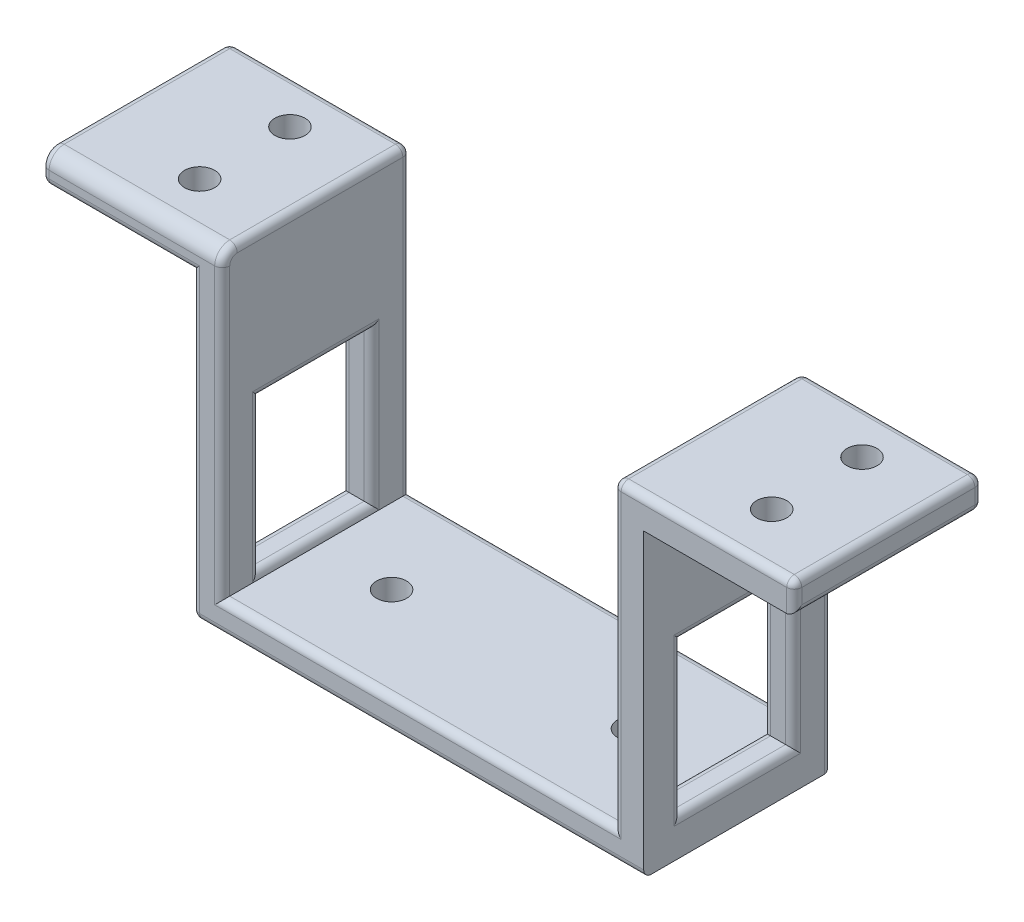
SolidWorks part; units mm, degrees
ref_plane "Front Plane" through (0, 0, 0) normal (0, 0, 1) x (1, 0, 0)
ref_plane "Top Plane" through (0, 0, 0) normal (0, 1, 0) x (1, 0, 0)
ref_plane "Right Plane" through (0, 0, 0) normal (1, 0, 0) x (0, 0, -1)
sketch "Sketch1" plane through (0, 0, 0) normal (0, 1, 0) x (1, 0, 0)
  line L1 (0, 0) -> (60, 0)
  line L2 (0, 0) -> (0, -25)
  line L3 (0, -25) -> (60, -25)
  line L4 (60, 0) -> (60, -25)
  dimension "D1" = 60
  dimension "D2" = 25
extrude "Boss-Extrude1" add sketch "Sketch1" along normal blind 4
sketch "Sketch2" plane through (0, 4, 0) normal (0, 1, 0) x (1, 0, 0)
  line L0 (0, -25) -> (60, -25) construction
  line L1 (0, 0) -> (4, 0)
  line L2 (0, 0) -> (0, -25)
  line L3 (0, -25) -> (4, -25)
  line L4 (4, 0) -> (4, -25)
  line L6 (60, 0) -> (56, 0)
  line L7 (60, 0) -> (60, -25)
  line L8 (60, -25) -> (56, -25)
  line L9 (56, 0) -> (56, -25)
  dimension "D1" = 4
  dimension "D2" = 4
extrude "Boss-Extrude2" add sketch "Sketch2" along normal blind 40
sketch "Sketch3" plane through (60, 0, 0) normal (1, 0, 0) x (0, 0, -1)
  line L0 (0, 44) -> (0, 0) construction
  line L1 (-25, 44) -> (0, 44)
  line L2 (-25, 44) -> (-25, 40)
  line L3 (-25, 40) -> (0, 40)
  line L4 (0, 44) -> (0, 40)
  dimension "D1" = 4
extrude "Boss-Extrude3" add sketch "Sketch3" along normal blind 20
sketch "Sketch4" plane through (0, 0, 0) normal (-1, 0, 0) x (0, 0, 1)
  line L0 (25, 44) -> (25, 0) construction
  line L1 (0, 44) -> (25, 44)
  line L2 (0, 44) -> (0, 40)
  line L3 (0, 40) -> (25, 40)
  line L4 (25, 44) -> (25, 40)
  dimension "D1" = 4
extrude "Boss-Extrude4" add sketch "Sketch4" along normal blind 20
sketch "Sketch5" plane through (0, 44, 0) normal (0, 1, 0) x (1, 0, 0)
  line L0 (56, -25) -> (80, -25) construction
  line L1 (-20, -25) -> (4, -25) construction
  line L2 (4, -25) -> (4, 0) construction
  line L3 (80, 0) -> (80, -25) construction
  circle A0 centre (-6, -6) radius 2
  circle A1 centre (-6, -18) radius 2
  circle A2 centre (70, -6) radius 2
  circle A3 centre (70, -18) radius 2
  dimension "D1" = 4
  dimension "D2" = 4
  dimension "D3" = 4
  dimension "D4" = 4
  dimension "D7" = 7
  dimension "D8" = 7
  dimension "D5" = 12
  dimension "D6" = 12
  dimension "D9" = 10
  dimension "D10" = 10
  dimension "D11" = 10
extrude "Cut-Extrude1" cut sketch "Sketch5" against normal blind 20
sketch "Sketch10" plane through (0, 0, 0) normal (-1, 0, 0) x (0, 0, 1)
  line L0 (0, 0) -> (25, 0) construction
  line L1 (5.1489, 25) -> (20, 25)
  line L2 (5.1489, 25) -> (5.1489, 5)
  line L3 (5.1489, 5) -> (20, 5)
  line L4 (20, 25) -> (20, 5)
  line L5 (25, 40) -> (25, 0) construction
  point P6 (12.5744, 5)
  dimension "D1" = 5
  dimension "D2" = 5
  dimension "D3" = 20
extrude "Cut-Extrude3" cut sketch "Sketch10" against normal blind 75
sketch "Sketch11" plane through (0, 4, 0) normal (0, 1, 0) x (1, 0, 0)
  line L0 (56, 0) -> (56, -25) construction
  line L1 (4, -25) -> (4, 0) construction
  line L2 (56, 0) -> (4, 0) construction
  circle A0 centre (14, -12.5) radius 2
  circle A1 centre (46, -12.5) radius 2
  dimension "D1" = 4
  dimension "D2" = 4
  dimension "D3" = 10
  dimension "D4" = 10
  dimension "D5" = 12.5
  dimension "D6" = 12.5
extrude "Cut-Extrude4" cut sketch "Sketch11" against normal blind 75
fillet "Fillet1" radius 2 1 edges at (-8, 44, 25)
fillet "Fillet2" radius 1 6 edges at (4, 44, 11.5) (4, 23, 25) (-20, 41, 25) (-20, 44, 11.5) (4, 43.4142, 24.4142) (-20, 43.4142, 24.4142)
fillet "Fillet3" radius 1 1 edges at (68, 44, 25)
fillet "Fillet4" radius 1 3 edges at (56, 23.5, 25) (56, 43.7071, 24.7071) (56, 44, 12)
fillet "Fillet5" radius 1 1 edges at (30, 4, 25)
fillet "Fillet6" radius 1 1 edges at (0, 5, 12.5744)
fillet "Fillet7" radius 1 1 edges at (0, 14.5, 5.1489)
fillet "Fillet8" radius 1 1 edges at (0, 25, 12.0744)
fillet "Fillet9" radius 1 1 edges at (0, 20, 25)
fillet "Fillet10" radius 1 1 edges at (56, 5, 12.5744)
fillet "Fillet11" radius 1 1 edges at (56, 14.5, 5.1489)
fillet "Fillet12" radius 1 1 edges at (56, 25, 12.0744)
fillet "Fillet13" radius 1 1 edges at (56, 15, 20)
fillet "Fillet14" radius 1 3 edges at (0, 0, 12) (0.2929, 0, 24.7071) (30.5, 0, 25)
fillet "Fillet15" radius 1 1 edges at (30, 4, 0)
fillet "Fillet16" radius 1 9 edges at (0, 20.5, 0) (0.2929, 0.2929, 0) (56.2929, 43.7071, 0) (30.5, 0, 0) (60, 20, 0) (80, 42, 0) (70, 40, 0) (68.5, 44, 0) (56, 23, 0)
fillet "Fillet17" radius 1 5 edges at (3.7071, 43.7071, 0) (-20, 41.5, 0) (-19.7071, 43.7071, 0) (4, 23, 0) (-8, 44, 0)
fillet "Fillet18" radius 1 5 edges at (-9, 40, 25) (-19.7071, 40, 24.7071) (-20, 40, 12.5) (-19.7071, 40, 0.2929) (-9, 40, 0)
fillet "Fillet19" radius 1 6 edges at (79.7071, 40.2929, 0.2929) (79.7071, 43.7071, 0.2929) (80, 41.5, 25) (80, 43.7071, 24.7071) (80, 40, 13) (80, 44, 12.5)
fillet "Fillet20" radius 1 4 edges at (60, 15, 5.1489) (60, 25, 12.5744) (60, 15, 20) (60, 5, 12.5744)
fillet "Fillet21" radius 1 4 edges at (4, 5, 12.5744) (4, 15, 5.1489) (4, 25, 12.5744) (4, 15, 20)
